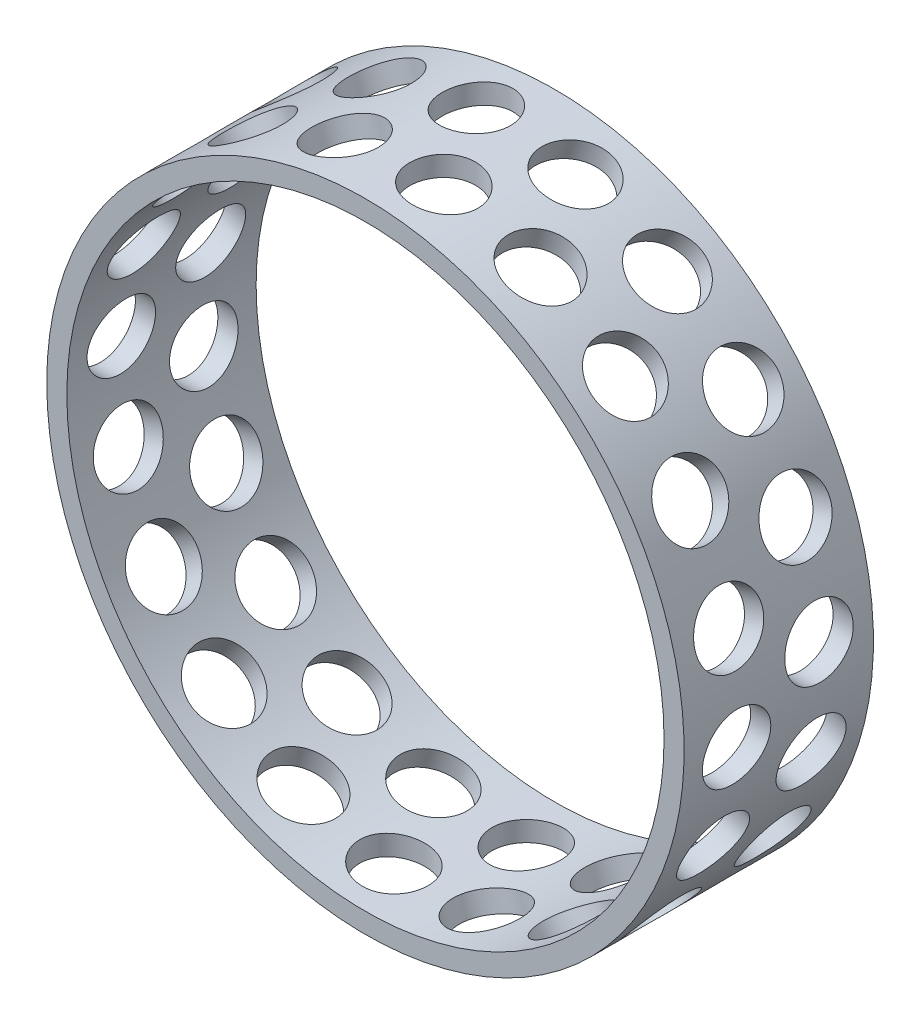
SolidWorks part; units mm, degrees
material "Plain Carbon Steel"
ref_plane "Front Plane" through (0, 0, 0) normal (0, 0, 1) x (1, 0, 0)
ref_plane "Top Plane" through (0, 0, 0) normal (0, 1, 0) x (1, 0, 0)
ref_plane "Right Plane" through (0, 0, 0) normal (1, 0, 0) x (0, 0, -1)
sketch "Sketch1" plane through (0, 0, 0) normal (1, 0, 0) x (0, 0, -1)
  line L0 (1, 79.375) -> (48.15, 79.375)
  line L1 (48.15, 79.375) -> (48.15, 74.375)
  line L2 (48.15, 74.375) -> (1, 74.375)
  line L3 (1, 74.375) -> (1, 79.375)
  dimension "D1" = 79.375
  dimension "D2" = 5
  dimension "D3" = 47.15
  dimension "D4" = 1
ref_axis "Axis1" through (0, 0, -50.5075) along (0, 0, 1)
revolve "Revolve1" add sketch "Sketch1" angle 360 about axis through (0, 0, -50.5075) along (0, 0, 1)
sketch "Sketch2" plane through (0, 0, 0) normal (1, 0, 0) x (0, 0, -1)
  line L0 (14.3098, 6.2149) -> (24.575, 0) construction
  line L1 (50.5075, 0) -> (-1.3575, 0) construction
  line L2 (24.575, 0) -> (34.8402, -6.2149) construction
  line L3 (1, 79.375) -> (1, -79.375) construction
  circle A0 centre (14.3098, 6.2149) radius 8.5
  circle A1 centre (34.8402, -6.2149) radius 8.5
  dimension "D1" = 17
  dimension "D2" = 12
  dimension "D3" = 23.575
extrude "Cut-Extrude1" cut sketch "Sketch2" against normal through all
pattern_circular "CirPattern1" count 20 over 360 about axis through (0, 0, -50.5075) along (0, 0, 1) of "Cut-Extrude1"
equation "\"TubeDiameter\" = 6.250in"
equation "\"D1@Sketch1\"=\"TubeDiameter\"/2"
